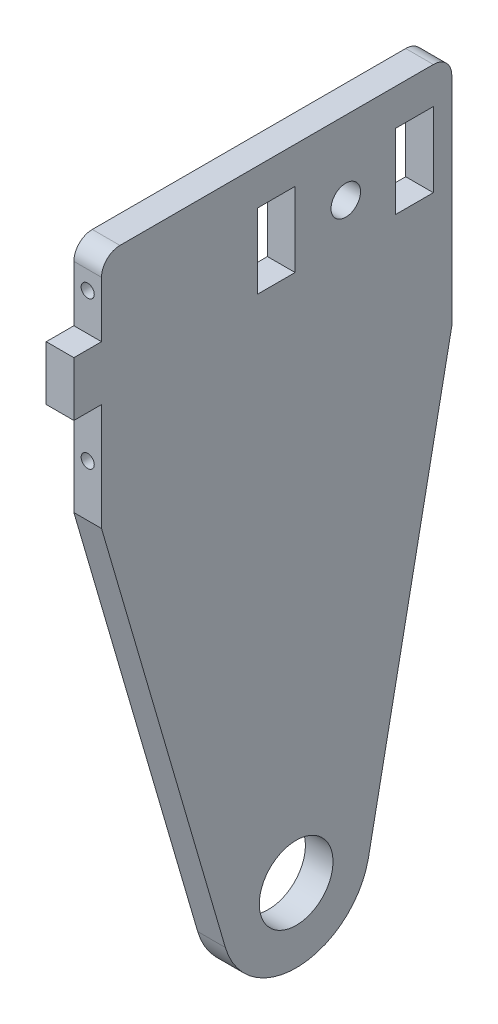
SolidWorks part; units mm, degrees
ref_plane "Front Plane" through (0, 0, 0) normal (0, 0, 1) x (1, 0, 0)
ref_plane "Top Plane" through (0, 0, 0) normal (0, 1, 0) x (1, 0, 0)
ref_plane "Right Plane" through (0, 0, 0) normal (1, 0, 0) x (0, 0, -1)
sketch "Sketch1" plane through (0, 0, 0) normal (1, 0, 0) x (0, 0, -1)
  line L0 (44.45, -27.94) -> (44.45, 9.5149)
  line L1 (-15.875, 9.525) -> (-15.875, -0.0762)
  line L2 (41.275, 12.7) -> (-12.7, 12.7)
  line L3 (41.275, 6.4262) -> (34.7726, 6.4262)
  line L4 (-15.875, -27.94) -> (5.4529, -101.1077)
  line L5 (44.45, -27.94) -> (30.1012, -100.0327)
  line L6 (34.7726, 6.4262) -> (34.7726, -6.4262)
  line L7 (34.7726, -6.4262) -> (41.275, -6.4262)
  line L8 (41.275, 6.4262) -> (41.275, -6.4262)
  line L9 (-15.875, -0.0762) -> (-20.6375, -0.0762)
  line L10 (10.9601, 6.4262) -> (17.4625, 6.4262)
  line L11 (10.9601, 6.4262) -> (10.9601, -6.4262)
  line L12 (10.9601, -6.4262) -> (17.4625, -6.4262)
  line L13 (17.4625, 6.4262) -> (17.4625, -6.4262)
  line L14 (-20.6375, -0.0762) -> (-20.6375, -9.4488)
  line L15 (-20.6375, -9.4488) -> (-15.875, -9.4488)
  line L16 (-15.875, -9.4488) -> (-15.875, -27.94)
  circle A0 centre (17.6455, -97.5536) radius 6.35
  arc A1 (5.4529, -101.1077) -> (30.1012, -100.0327) centre (17.6455, -97.5536) ccw
  circle A2 centre (26.1937, 0) radius 2.54
  arc A4 (44.45, 9.5149) -> (41.275, 12.7) centre (41.275, 9.525) ccw
  circle A5 centre (17.6455, -97.5536) radius 82.55 construction
  arc A10 (-15.875, 9.525) -> (-12.7, 12.7) centre (-12.7, 9.525) cw
  point P10 (34.7726, 0)
  point P23 (17.4625, 0)
  dimension "D1" = 3.175
  dimension "D2" = 12.8524
  dimension "D3" = 165.1
  dimension "D4" = 12.7
  dimension "D6" = 3.175
  dimension "D9" = 57.15
  dimension "D13" = 9.3726
  dimension "D15" = 30.3149
  dimension "D7" = 12.7
  dimension "D10" = 5.08
  dimension "D5" = 6.5024
  dimension "D8" = 6.5024
  dimension "D11" = 15.875
  dimension "D12" = 12.7762
  dimension "D14" = 4.7625
  dimension "D16" = 18.2562
extrude "Boss-Extrude1" add sketch "Sketch1" along normal blind 4.7625
sketch "Sketch2" plane through (0, 0, 15.875) normal (0, 0, 1) x (1, 0, 0)
  line L0 (4.7625, 12.7) -> (0, 12.7) construction
  line L1 (4.7625, 9.525) -> (0, 9.525) construction
  circle A0 centre (2.3813, 6.35) radius 1.1303
  circle A1 centre (2.3813, -19.05) radius 1.1303
  point P8 (2.3813, 9.525)
  dimension "D3" = 2.2606
  dimension "D1" = 6.35
  dimension "D2" = 31.75
extrude "Cut-Extrude1" cut sketch "Sketch2" against normal blind 12.7
